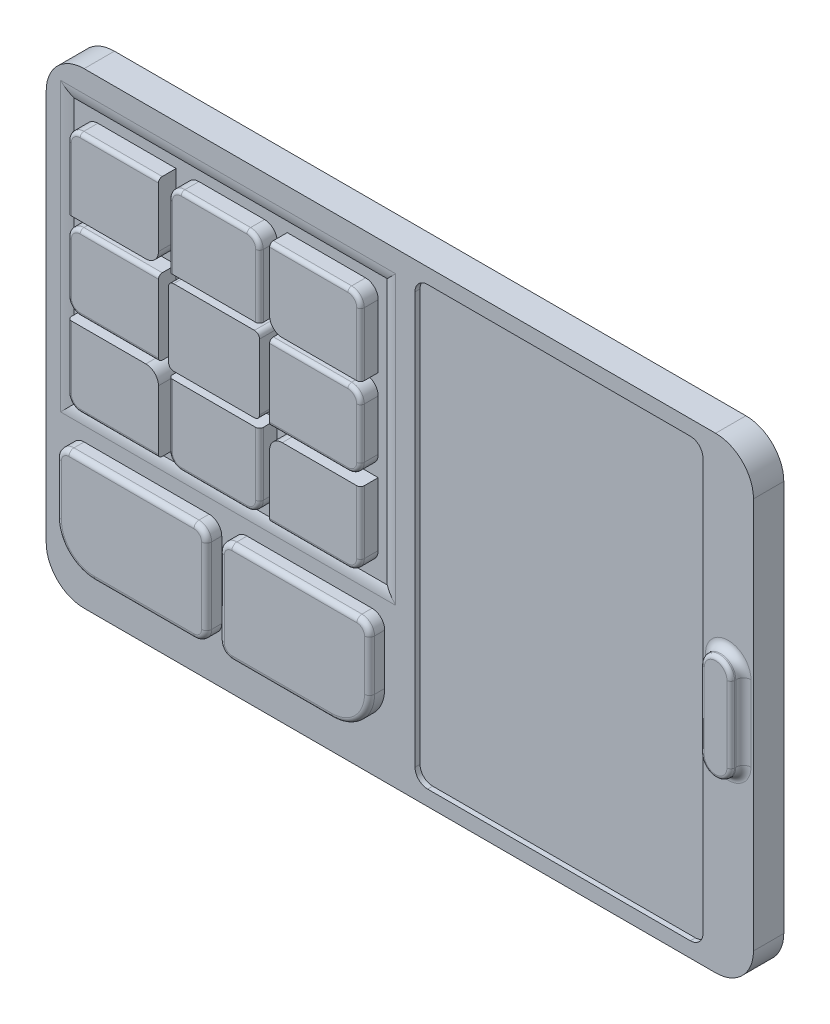
SolidWorks part; units mm, degrees
ref_plane "前视基准面" through (0, 0, 0) normal (0, 0, 1) x (1, 0, 0)
ref_plane "上视基准面" through (0, 0, 0) normal (0, 1, 0) x (1, 0, 0)
ref_plane "右视基准面" through (0, 0, 0) normal (1, 0, 0) x (0, 0, -1)
sketch "草图2" plane through (0, 0, 0) normal (0, 0, 1) x (1, 0, 0)
  line L0 (0, 0) -> (0, 75) construction
  line L1 (-140, 92.5) -> (140, 92.5)
  line L2 (-140, 92.5) -> (-140, -92.5)
  line L3 (-140, -92.5) -> (140, -92.5)
  line L4 (140, 92.5) -> (140, -92.5)
  line L5 (-140, 92.5) -> (140, -92.5) construction
  line L6 (-140, -92.5) -> (140, 92.5) construction
  line L7 (-85.5619, 75.5) -> (-85.5619, 45.5)
  line L8 (-130, 79.5) -> (-6, 79.5)
  line L9 (-130, 79.5) -> (-130, -25.5)
  line L10 (-130, -25.5) -> (-6, -25.5)
  line L11 (-6, 79.5) -> (-6, -25.5)
  line L12 (-130, 79.5) -> (-6, -25.5) construction
  line L13 (-130, -25.5) -> (-6, 79.5) construction
  line L14 (-125.5619, 75.5) -> (-89.5619, 75.5)
  line L15 (-125.5619, 75.5) -> (-125.5619, 45.5)
  line L16 (-125.5619, 45.5) -> (-89.5619, 45.5)
  line L17 (-89.5619, 75.5) -> (-89.5619, 45.5)
  line L18 (-125.5619, 75.5) -> (-89.5619, 45.5) construction
  line L19 (-125.5619, 45.5) -> (-89.5619, 75.5) construction
  line L20 (-85.5619, 75.5) -> (-49.5619, 75.5)
  line L21 (-49.5619, 75.5) -> (-49.5619, 45.5)
  line L22 (-85.5619, 45.5) -> (-49.5619, 45.5)
  line L23 (-45.5619, 75.5) -> (-45.5619, 45.5)
  line L24 (-45.5619, 75.5) -> (-9.5619, 75.5)
  line L25 (-9.5619, 75.5) -> (-9.5619, 45.5)
  line L26 (-45.5619, 45.5) -> (-9.5619, 45.5)
  line L27 (-85.5619, 42.5) -> (-85.5619, 12.5)
  line L28 (-85.5619, 42.5) -> (-49.5619, 42.5)
  line L29 (-49.5619, 42.5) -> (-49.5619, 12.5)
  line L30 (-85.5619, 12.5) -> (-49.5619, 12.5)
  line L31 (-45.5619, 42.5) -> (-45.5619, 12.5)
  line L32 (-45.5619, 42.5) -> (-9.5619, 42.5)
  line L33 (-9.5619, 42.5) -> (-9.5619, 12.5)
  line L34 (-45.5619, 12.5) -> (-9.5619, 12.5)
  line L35 (-85.5619, 9.5) -> (-85.5619, -20.5)
  line L36 (-85.5619, 9.5) -> (-49.5619, 9.5)
  line L37 (-49.5619, 9.5) -> (-49.5619, -20.5)
  line L38 (-85.5619, -20.5) -> (-49.5619, -20.5)
  line L39 (-45.5619, 9.5) -> (-45.5619, -20.5)
  line L40 (-45.5619, 9.5) -> (-9.5619, 9.5)
  line L41 (-9.5619, 9.5) -> (-9.5619, -20.5)
  line L42 (-45.5619, -20.5) -> (-9.5619, -20.5)
  line L43 (-125.5619, 42.5) -> (-125.5619, 12.5)
  line L44 (-125.5619, 42.5) -> (-89.5619, 42.5)
  line L45 (-89.5619, 42.5) -> (-89.5619, 12.5)
  line L46 (-125.5619, 12.5) -> (-89.5619, 12.5)
  line L47 (-125.5619, 9.5) -> (-125.5619, -20.5)
  line L48 (-125.5619, 9.5) -> (-89.5619, 9.5)
  line L49 (-89.5619, 9.5) -> (-89.5619, -20.5)
  line L50 (-125.5619, -20.5) -> (-89.5619, -20.5)
  line L51 (-130, -35.5) -> (-6, -35.5)
  line L52 (6, 86.5) -> (120, 86.5)
  line L53 (6, 86.5) -> (6, -86.5)
  line L54 (6, -86.5) -> (120, -86.5)
  line L55 (120, 86.5) -> (120, -86.5)
  line L56 (6, 86.5) -> (120, -86.5) construction
  line L57 (6, -86.5) -> (120, 86.5) construction
  line L58 (-130, -35.5) -> (-130, -75.5)
  line L59 (-6, -35.5) -> (-6, -75.5)
  line L60 (-130, -75.5) -> (-6, -75.5)
  line L61 (-130, -35.5) -> (-6, -75.5) construction
  line L63 (-70.5, -35.5) -> (-65.5, -35.5)
  line L64 (-70.5, -35.5) -> (-70.5, -75.5)
  line L65 (-70.5, -75.5) -> (-65.5, -75.5)
  line L66 (-65.5, -35.5) -> (-65.5, -75.5)
  line L67 (-70.5, -35.5) -> (-65.5, -75.5) construction
  line L68 (-70.5, -75.5) -> (-65.5, -35.5) construction
  point P0 (0, 0)
  point P7 (-107.5619, 60.5)
  point P10 (-68, 27)
  point P18 (63, 0)
  point P21 (-67.5619, 60.5)
  point P26 (-27.5619, 60.5)
  point P31 (-67.5619, 27.5)
  point P36 (-27.5619, 27.5)
  point P41 (-67.5619, -5.5)
  point P46 (-27.5619, -5.5)
  point P51 (-107.5619, 27.5)
  point P56 (-107.5619, -5.5)
  point P63 (-68, -55.5)
  dimension "D1" = 185
  dimension "D2" = 280
  dimension "D3" = 124
  dimension "D4" = 105
  dimension "D5" = 13
  dimension "D6" = 10
  dimension "D7" = 36
  dimension "D8" = 30
  dimension "D9" = 4
  dimension "D12" = 20
  dimension "D13" = 6
  dimension "D14" = 6
  dimension "D15" = 6
  dimension "D16" = 10
  dimension "D17" = 40
  dimension "D18" = 124
  dimension "D19" = 5
  dimension "D10" = 3
  dimension "D11" = 3
extrude "凸台-拉伸1" add sketch "草图2" along normal blind 12 contours L1 L4 L3 L2
extrude "切除-拉伸1" cut sketch "草图2<4>" against normal blind 1 from surface contours L11 L10 L9 L8 starting at face at (0, 0, 12)
sketch "草图2<4>" plane through (0, 0, 0) normal (0, 0, 1) x (1, 0, 0) same geometry as "草图2"
extrude "凸台-拉伸2" add sketch "草图2<3>" along normal blind 18 contours L47 L50 L49 L48 | L35 L38 L37 L36 | L39 L42 L41 L40 | L31 L34 L33 L32 | L27 L30 L29 L28 | L43 L46 L45 L44 | L17 L14 L15 L16 | L7 L22 L21 L20 | L23 L26 L25 L24 region at (-67.5619, 60.5, 0) region at (-107.5619, 60.5, 0) region at (-27.5619, 60.5, 0) region at (-67.5619, 27.5, 0) region at (-27.5619, 27.5, 0) region at (-67.5619, -5.5, 0) region at (-27.5619, -5.5, 0) region at (-107.5619, 27.5, 0) region at (-107.5619, -5.5, 0)
sketch "草图2<3>" plane through (0, 0, 0) normal (0, 0, 1) x (1, 0, 0) same geometry as "草图2"
fillet "圆角1" radius 10 4 edges at (-130, 27, 12) (-68, -25.5, 12) (-68, 79.5, 12) (-6, 27, 12)
extrude "切除-拉伸2" cut sketch "草图2<5>" against normal blind 2 from surface contours L55 L52 L53 L54 region at (63, 0, 0) starting at face at (-68, 27, 12)
sketch "草图2<5>" plane through (0, 0, 0) normal (0, 0, 1) x (1, 0, 0) same geometry as "草图2"
fillet "圆角3" radius 5 4 edges at (6, -86.5, 11) (120, -86.5, 11) (120, 86.5, 11) (6, 86.5, 11)
extrude "凸台-拉伸3" add sketch "草图2<7>" along normal blind 18 contours L64 L51 L58 L60 | L51 L66 L60 L59 region at (-100.25, -55.5, 0) region at (-35.75, -55.5, 0)
sketch "草图2<7>" plane through (0, 0, 0) normal (0, 0, 1) x (1, 0, 0) same geometry as "草图2"
fillet "圆角7" radius 15 4 edges at (-140, -92.5, 6) (140, -92.5, 6) (-140, 92.5, 6) (140, 92.5, 6)
fillet "圆角8" radius 5 5 edges at (-130, -35.5, 15) (-70.5, -35.5, 15) (-65.5, -75.5, 15) (-65.5, -35.5, 15) (-6, -35.5, 15)
fillet "圆角9" radius 15 2 edges at (-6, -75.5, 15) (-130, -75.5, 15)
fillet "圆角10" radius 5 4 edges at (-125.5619, 75.5, 14.5) (-125.5619, -20.5, 14.5) (-9.5619, -20.5, 14.5) (-9.5619, 75.5, 14.5)
sketch "草图4" plane through (0, 0, 12) normal (0, 0, 1) x (1, 0, 0)
  line L0 (130, 15) -> (130, -15) construction
  line L1 (136, 15) -> (136, -15)
  line L2 (124, 15) -> (124, -15)
  line L3 (-125, 92.5) -> (125, 92.5) construction
  line L4 (-125, -92.5) -> (125, -92.5) construction
  line L5 (120, -81.5) -> (120, 81.5) construction
  arc A0 (136, 15) -> (124, 15) centre (130, 15) ccw
  arc A1 (124, -15) -> (136, -15) centre (130, -15) ccw
  point P2 (130, 0)
  point P11 (136.0153, 15)
  dimension "D1" = 12
  dimension "D2" = 30
  dimension "D3" = 92.5
  dimension "D4" = 92.5
  dimension "D5" = 4
extrude "凸台-拉伸4" add sketch "草图4" along normal blind 5
fillet "圆角11" radius 3 4 edges at (130, -21, 12) (124, 0, 12) (130, 21, 12) (136, 0, 12)
fillet "圆角12" radius 1.5 4 edges at (130, -21, 17) (124, 0, 17) (130, 21, 17) (136, 0, 17)
fillet "圆角13" radius 5 1 edges at (-70.5, -75.5, 15)
fillet "圆角14" radius 5 4 edges at (-89.5619, 9.5, 14.5) (-45.5619, 9.5, 14.5) (-45.5619, 45.5, 14.5) (-89.5619, 45.5, 14.5)
fillet "圆角15" radius 5 8 edges at (-49.5619, -20.5, 14.5) (-85.5619, -20.5, 14.5) (-85.5619, 75.5, 14.5) (-49.5619, 75.5, 14.5) (-9.5619, 12.5, 14.5) (-9.5619, 42.5, 14.5) (-125.5619, 12.5, 14.5) (-125.5619, 42.5, 14.5)
fillet "圆角16" radius 2 16 edges at (-64.0355, -74.0355, 18) (-65.5, -55.5, 18) (-64.0355, -36.9645, 18) (-35.75, -35.5, 18) (-7.4645, -36.9645, 18) (-6, -50.5, 18) (-10.3934, -71.1066, 18) (-125.6066, -71.1066, 18) (-130, -50.5, 18) (-128.5355, -36.9645, 18) (-100.25, -35.5, 18) (-71.9645, -36.9645, 18) (-70.5, -55.5, 18) (-71.9645, -74.0355, 18) (-40.75, -75.5, 18) (-95.25, -75.5, 18)
fillet "圆角17" radius 1.5 32 edges at (-85.5619, -3, 18) (-84.0974, -19.0355, 18) (-49.5619, -3, 18) (-51.0264, -19.0355, 18) (-49.5619, 58, 18) (-85.5619, 58, 18) (-84.0974, 74.0355, 18) (-67.5619, 75.5, 18) (-30.0619, 42.5, 18) (-11.0264, 41.0355, 18) (-30.0619, 12.5, 18) (-11.0264, 13.9645, 18) (-105.0619, 42.5, 18) (-124.0974, 41.0355, 18) (-105.0619, 12.5, 18) (-124.0974, 13.9645, 18) (-105.0619, -20.5, 18) (-124.0974, -19.0355, 18) (-30.0619, 75.5, 18) (-11.0264, 74.0355, 18) (-30.0619, -20.5, 18) (-11.0264, -19.0355, 18) (-105.0619, 75.5, 18) (-124.0974, 74.0355, 18) (-67.5619, -20.5, 18) (-51.0264, 74.0355, 18) (-9.5619, 27.5, 18) (-125.5619, 27.5, 18) (-125.5619, -3, 18) (-9.5619, 58, 18) (-9.5619, -3, 18) (-125.5619, 58, 18)
fillet "圆角18" radius 2 4 edges at (-85.5619, 12.5, 14.5) (-85.5619, 42.5, 14.5) (-49.5619, 42.5, 14.5) (-49.5619, 12.5, 14.5)
